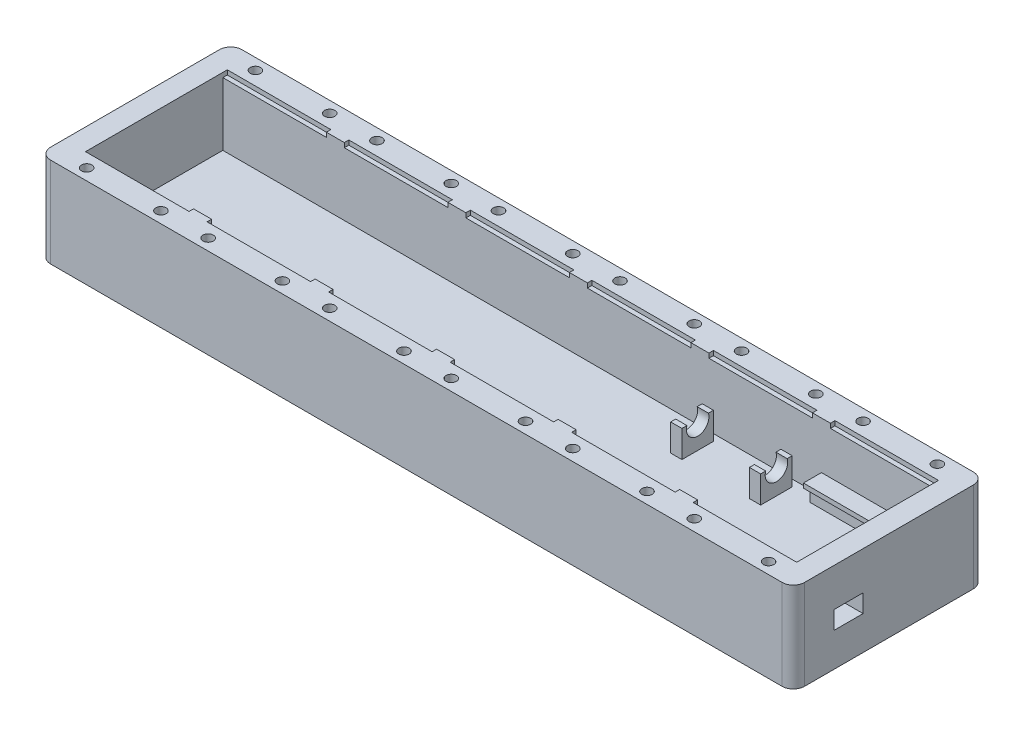
SolidWorks part; units mm, degrees
material "Starkstromplatine"
ref_plane "Ebene vorne" through (0, 0, 0) normal (0, 0, 1) x (1, 0, 0)
ref_plane "Ebene oben" through (0, 0, 0) normal (0, 1, 0) x (1, 0, 0)
ref_plane "Ebene rechts" through (0, 0, 0) normal (1, 0, 0) x (0, 0, -1)
sketch "Skizze2" plane through (0, 0, 0) normal (0, 0, 1) x (1, 0, 0)
  line L1 (0, 0) -> (335, 0)
  line L2 (0, 0) -> (0, 40)
  line L3 (0, 40) -> (335, 40)
  line L4 (335, 0) -> (335, 40)
  dimension "D1" = 335
  dimension "D2" = 40
extrude "Aufsatz-Linear austragen1" add sketch "Skizze2" along normal blind 85
sketch "Skizze4" plane through (0, 40, 0) normal (0, 1, 0) x (1, 0, 0)
  line L1 (9.5, -13) -> (325.5, -13)
  line L2 (9.5, -13) -> (9.5, -72)
  line L3 (9.5, -72) -> (325.5, -72)
  line L4 (325.5, -13) -> (325.5, -72)
  line L6 (0, -85) -> (0, 0) construction
  line L7 (335, -85) -> (335, 0) construction
  line L8 (335, -85) -> (0, -85) construction
  dimension "D1" = 59
  dimension "D2" = 13
  dimension "D3" = 9.5
  dimension "D4" = 9.5
extrude "Schnitt-Linear austragen1" cut sketch "Skizze4" against normal blind 30
sketch "Skizze11" plane through (0, 40, 0) normal (0, 1, 0) x (1, 0, 0)
  line L0 (9.5, -72) -> (325.5, -72) construction
  line L1 (9.5, -13) -> (55.5, -13)
  line L2 (9.5, -13) -> (9.5, -11)
  line L3 (9.5, -11) -> (55.5, -11)
  line L4 (55.5, -13) -> (55.5, -11)
  line L5 (55.5, -72) -> (9.5, -72)
  line L6 (55.5, -72) -> (55.5, -74)
  line L7 (55.5, -74) -> (9.5, -74)
  line L8 (9.5, -72) -> (9.5, -74)
  line L9 (325.5, -13) -> (9.5, -13) construction
  line L10 (63.5, -74) -> (109.5, -74)
  line L11 (63.5, -74) -> (63.5, -72)
  line L12 (63.5, -72) -> (109.5, -72)
  line L13 (109.5, -74) -> (109.5, -72)
  line L14 (117.5, -74) -> (163.5, -74)
  line L15 (117.5, -74) -> (117.5, -72)
  line L16 (117.5, -72) -> (163.5, -72)
  line L17 (163.5, -74) -> (163.5, -72)
  line L18 (171.5, -74) -> (217.5, -74)
  line L19 (171.5, -74) -> (171.5, -72)
  line L20 (171.5, -72) -> (217.5, -72)
  line L21 (217.5, -74) -> (217.5, -72)
  line L22 (225.5, -74) -> (271.5, -74)
  line L23 (225.5, -74) -> (225.5, -72)
  line L24 (225.5, -72) -> (271.5, -72)
  line L25 (271.5, -74) -> (271.5, -72)
  line L26 (279.5, -74) -> (325.5, -74)
  line L27 (279.5, -74) -> (279.5, -72)
  line L28 (279.5, -72) -> (325.5, -72)
  line L29 (325.5, -74) -> (325.5, -72)
  line L30 (325.5, -13) -> (279.5, -13)
  line L31 (325.5, -13) -> (325.5, -11)
  line L32 (325.5, -11) -> (279.5, -11)
  line L33 (279.5, -13) -> (279.5, -11)
  line L34 (0, -85) -> (0, 0) construction
  line L35 (271.5, -13) -> (225.5, -13)
  line L36 (271.5, -13) -> (271.5, -11)
  line L37 (271.5, -11) -> (225.5, -11)
  line L38 (225.5, -13) -> (225.5, -11)
  line L39 (217.5, -13) -> (171.5, -13)
  line L40 (217.5, -13) -> (217.5, -11)
  line L41 (217.5, -11) -> (171.5, -11)
  line L42 (171.5, -13) -> (171.5, -11)
  line L43 (163.5, -13) -> (117.5, -13)
  line L44 (163.5, -13) -> (163.5, -11)
  line L45 (163.5, -11) -> (117.5, -11)
  line L46 (117.5, -13) -> (117.5, -11)
  line L47 (109.5, -13) -> (63.5, -13)
  line L48 (109.5, -13) -> (109.5, -11)
  line L49 (109.5, -11) -> (63.5, -11)
  line L50 (63.5, -13) -> (63.5, -11)
  dimension "D1" = 46
  dimension "D2" = 2
  dimension "D3" = 46
  dimension "D4" = 8
  dimension "D5" = 8
  dimension "D6" = 8
  dimension "D7" = 8
  dimension "D8" = 8
  dimension "D9" = 8
  dimension "D10" = 46
  dimension "D11" = 46
  dimension "D12" = 46
  dimension "D13" = 46
  dimension "D14" = 46
  dimension "D15" = 8
  dimension "D16" = 8
  dimension "D17" = 8
  dimension "D18" = 8
  dimension "D19" = 46
  dimension "D20" = 46
  dimension "D21" = 46
  dimension "D22" = 46
  dimension "D23" = 2
  dimension "D24" = 2
  dimension "D25" = 2
  dimension "D26" = 2
  dimension "D27" = 2
  dimension "D28" = 2
  dimension "D29" = 2
  dimension "D30" = 2
  dimension "D31" = 46
  dimension "D32" = 9.5
  dimension "D33" = 9.5
  dimension "D34" = 2
  dimension "D35" = 2
extrude "Schnitt-Linear austragen4" cut sketch "Skizze11" against normal blind 2
sketch "Skizze17" plane through (0, 40, 0) normal (0, 1, 0) x (1, 0, 0)
  line L0 (55.5, -74) -> (55.5, -72) construction
  line L1 (335, 0) -> (0, 0) construction
  line L2 (335, -85) -> (0, -85) construction
  line L3 (9.5, -72) -> (9.5, -74) construction
  line L4 (9.5, -11) -> (9.5, -74) construction
  line L5 (55.5, -13) -> (55.5, -11) construction
  line L6 (63.5, -72) -> (63.5, -74) construction
  line L7 (109.5, -74) -> (109.5, -72) construction
  line L8 (163.5, -74) -> (163.5, -72) construction
  line L9 (109.5, -13) -> (109.5, -11) construction
  line L10 (171.5, -72) -> (171.5, -74) construction
  line L11 (217.5, -74) -> (217.5, -72) construction
  line L12 (325.5, -74) -> (325.5, -11) construction
  line L13 (279.5, -72) -> (279.5, -74) construction
  line L14 (271.5, -74) -> (271.5, -72) construction
  line L15 (225.5, -72) -> (225.5, -74) construction
  line L16 (63.5, -11) -> (63.5, -13) construction
  line L17 (163.5, -13) -> (163.5, -11) construction
  line L18 (117.5, -11) -> (117.5, -13) construction
  line L19 (171.5, -11) -> (171.5, -13) construction
  line L20 (225.5, -11) -> (225.5, -13) construction
  line L21 (271.5, -13) -> (271.5, -11) construction
  line L22 (279.5, -11) -> (279.5, -13) construction
  line L23 (325.5, -13) -> (325.5, -11) construction
  line L24 (117.5, -72) -> (117.5, -74) construction
  circle A0 centre (49, -80) radius 2.3
  circle A1 centre (16, -80) radius 2.3
  circle A2 centre (16, -5) radius 2.3
  circle A3 centre (49, -5) radius 2.3
  circle A4 centre (70, -5) radius 2.3
  circle A5 centre (103, -5) radius 2.3
  circle A6 centre (70, -80) radius 2.3
  circle A7 centre (103, -80) radius 2.3
  circle A8 centre (124, -80) radius 2.3
  circle A9 centre (157, -80) radius 2.3
  circle A10 centre (178, -80) radius 2.3
  circle A11 centre (211, -80) radius 2.3
  circle A12 centre (232, -80) radius 2.3
  circle A13 centre (265, -80) radius 2.3
  circle A14 centre (286, -80) radius 2.3
  circle A15 centre (319, -80) radius 2.3
  circle A16 centre (319, -5) radius 2.3
  circle A17 centre (286, -5) radius 2.3
  circle A18 centre (265, -5) radius 2.3
  circle A19 centre (232, -5) radius 2.3
  circle A20 centre (211, -5) radius 2.3
  circle A21 centre (178, -5) radius 2.3
  circle A22 centre (157, -5) radius 2.3
  circle A23 centre (124, -5) radius 2.3
  dimension "D1" = 4.6
  dimension "D2" = 4.6
  dimension "D3" = 4.6
  dimension "D4" = 4.6
  dimension "D5" = 5
  dimension "D6" = 5
  dimension "D7" = 5
  dimension "D8" = 5
  dimension "D10" = 6.5
  dimension "D11" = 6.5
  dimension "D12" = 6.5
  dimension "D13" = 4.6
  dimension "D14" = 4.6
  dimension "D15" = 4.6
  dimension "D16" = 4.6
  dimension "D17" = 4.6
  dimension "D18" = 4.6
  dimension "D19" = 4.6
  dimension "D20" = 4.6
  dimension "D21" = 4.6
  dimension "D22" = 4.6
  dimension "D23" = 6.5
  dimension "D25" = 5
  dimension "D26" = 5
  dimension "D27" = 6.5
  dimension "D28" = 5
  dimension "D29" = 6.5
  dimension "D30" = 5
  dimension "D31" = 6.5
  dimension "D32" = 5
  dimension "D33" = 5
  dimension "D34" = 5
  dimension "D35" = 5
  dimension "D36" = 5
  dimension "D37" = 6.5
  dimension "D38" = 6.5
  dimension "D39" = 6.5
  dimension "D40" = 6.5
  dimension "D41" = 5
  dimension "D42" = 6.5
  dimension "D43" = 4.6
  dimension "D44" = 4.6
  dimension "D45" = 4.6
  dimension "D46" = 4.6
  dimension "D47" = 4.6
  dimension "D48" = 4.6
  dimension "D49" = 4.6
  dimension "D50" = 4.6
  dimension "D51" = 4.6
  dimension "D52" = 4.6
  dimension "D53" = 5
  dimension "D54" = 6.5
  dimension "D55" = 5
  dimension "D56" = 6.5
  dimension "D58" = 6.5
  dimension "D62" = 6.5
  dimension "D63" = 6.5
  dimension "D64" = 6.5
  dimension "D9" = 6.5
  dimension "D24" = 6.5
  dimension "D57" = 6.5
  dimension "D59" = 6.5
  dimension "D60" = 6.5
  dimension "D61" = 6.5
extrude "Schnitt-Linear austragen6" cut sketch "Skizze17" against normal blind 4
fillet "Verrundung2" radius 5 1 edges at (0, 20, 85)
fillet "Verrundung3" radius 5 1 edges at (0, 20, 0)
fillet "Verrundung4" radius 5 1 edges at (335, 20, 0)
fillet "Verrundung6" radius 5 1 edges at (335, 20, 85)
sketch "Skizze18" plane through (325.5, 0, 0) normal (-1, 0, 0) x (0, 0, 1)
  line L0 (72, 10) -> (72, 38) construction
  line L1 (54, 23) -> (67, 23)
  line L2 (54, 23) -> (54, 15)
  line L3 (54, 15) -> (67, 15)
  line L4 (67, 23) -> (67, 15)
  line L5 (72, 10) -> (13, 10) construction
  dimension "D1" = 5
  dimension "D2" = 13
  dimension "D3" = 8
  dimension "D4" = 5
  dimension "D5" = 5
extrude "Schnitt-Linear austragen7" cut sketch "Skizze18" against normal blind 10
sketch "Skizze20" plane through (0, 10, 0) normal (0, 1, 0) x (1, 0, 0)
  line L0 (325.5, -13) -> (9.5, -13) construction
  line L1 (260.5, -16) -> (265.5, -16)
  line L2 (260.5, -16) -> (260.5, -30)
  line L3 (260.5, -30) -> (265.5, -30)
  line L4 (265.5, -16) -> (265.5, -30)
  line L5 (225.5, -16) -> (230.5, -16)
  line L6 (225.5, -16) -> (225.5, -30)
  line L7 (225.5, -30) -> (230.5, -30)
  line L8 (230.5, -16) -> (230.5, -30)
  line L9 (325.5, -72) -> (325.5, -13) construction
  dimension "D1" = 14
  dimension "D2" = 14
  dimension "D3" = 5
  dimension "D4" = 5
  dimension "D5" = 3
  dimension "D6" = 3
  dimension "D7" = 30
  dimension "D8" = 60
extrude "Aufsatz-Linear austragen2" add sketch "Skizze20" along normal blind 12
sketch "Skizze21" plane through (225.5, 0, 0) normal (-1, 0, 0) x (0, 0, 1)
  line L0 (16, 22) -> (16, 10) construction
  line L1 (16, 22) -> (30, 22) construction
  circle A0 centre (23, 20.5) radius 5
  dimension "D1" = 7
  dimension "D2" = 1.5
extrude "Schnitt-Linear austragen8" cut sketch "Skizze21" against normal blind 71
sketch "Skizze22" plane through (0, 0, 13) normal (0, 0, 1) x (1, 0, 0)
  line L0 (325.5, 10) -> (325.5, 38) construction
  line L1 (325.5, 10) -> (275.5, 10)
  line L2 (325.5, 10) -> (325.5, 19)
  line L3 (325.5, 19) -> (275.5, 19)
  line L4 (275.5, 10) -> (275.5, 19)
  line L5 (325.5, 10) -> (9.5, 10) construction
  dimension "D1" = 0
  dimension "D2" = 9
  dimension "D3" = 50
extrude "Aufsatz-Linear austragen3" add sketch "Skizze22" along normal blind 5
sketch "Skizze23" plane through (0, 0, 18) normal (0, 0, 1) x (1, 0, 0)
  line L0 (325.5, 10) -> (325.5, 19) construction
  line L1 (275.5, 19) -> (325.5, 19)
  line L2 (275.5, 19) -> (275.5, 17)
  line L3 (275.5, 17) -> (325.5, 17)
  line L4 (325.5, 19) -> (325.5, 17)
  dimension "D1" = 2
extrude "Aufsatz-Linear austragen4" add sketch "Skizze23" along normal blind 3
